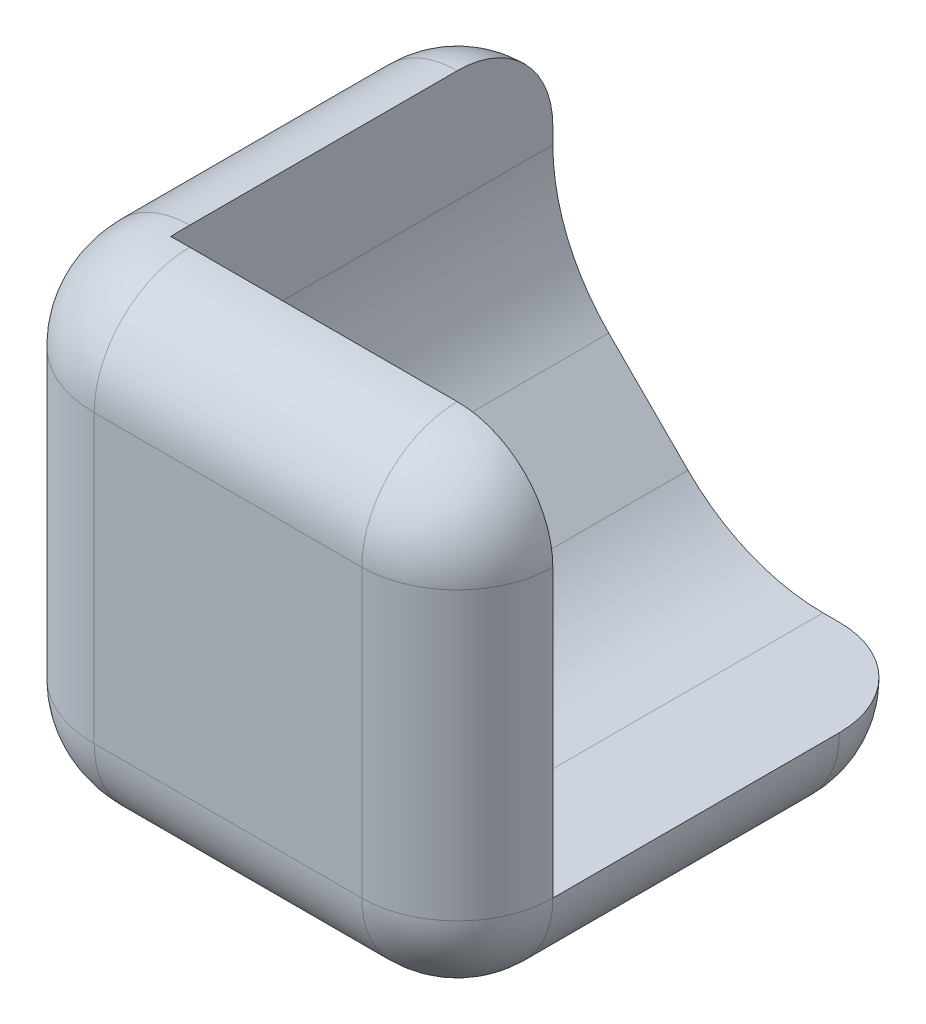
SolidWorks part; units mm, degrees
ref_plane "Front Plane" through (0, 0, 0) normal (0, 0, 1) x (1, 0, 0)
ref_plane "Top Plane" through (0, 0, 0) normal (0, 1, 0) x (1, 0, 0)
ref_plane "Right Plane" through (0, 0, 0) normal (1, 0, 0) x (0, 0, -1)
sketch "Sketch1" plane through (0, 0, 0) normal (0, 1, 0) x (1, 0, 0)
  line L1 (-10, 10) -> (10, 10)
  line L2 (-10, 10) -> (-10, -10)
  line L3 (-10, -10) -> (10, -10)
  line L4 (10, 10) -> (10, -10)
  line L5 (0, -10) -> (0, 10) construction
  line L6 (-10, 0) -> (10, 0) construction
  line L7 (20, 20) -> (0, 20)
  line L8 (20, 20) -> (20, 0)
  line L9 (20, 0) -> (0, 0)
  line L10 (0, 20) -> (0, 0)
  line L11 (10, 0) -> (10, 20) construction
  line L12 (20, 10) -> (0, 10) construction
  point P0 (0, 0)
  dimension "D1" = 20
  dimension "D2" = 20
extrude "Boss-Extrude1" add sketch "Sketch1" along normal blind 20 contours L10 L1 L2 L3 L4 L9 | L1 L10 L9 L4 region at (-1.6667, 0, 1.6667) region at (5, 0, -5)
sketch "Sketch2" plane through (0, 20, 0) normal (0, 1, 0) x (1, 0, 0)
  line L1 (20, 20) -> (0, 20)
  line L2 (20, 20) -> (20, 0)
  line L3 (20, 0) -> (0, 0)
  line L4 (0, 20) -> (0, 0)
  line L5 (10, 0) -> (10, 20) construction
  line L6 (20, 10) -> (0, 10) construction
  point P0 (10, 10)
extrude "Cut-Extrude1" cut sketch "Sketch2" against normal blind 10
sketch "Sketch3" plane through (0, 0, 0) normal (0, 0, -1) x (-1, 0, 0)
  line L0 (-10, 10) -> (-7.0711, 10)
  line L1 (-10, 10) -> (0, 10) construction
  line L2 (-3.5355, 11.4645) -> (-1.4645, 13.5355)
  line L3 (0, 10) -> (0, 20) construction
  line L4 (0, 17.0711) -> (0, 20)
  line L6 (0, 10) -> (-10, 10)
  line L7 (0, 10) -> (0, 20)
  arc A0 (-1.4645, 13.5355) -> (0, 17.0711) centre (-5, 17.0711) ccw
  arc A1 (-7.0711, 10) -> (-3.5355, 11.4645) centre (-7.0711, 15) ccw
  point P12 (0, 15)
  point P15 (-5, 10)
  line M3 (-10, 10) -> (0, 10)
  line M4 (0, 10) -> (0, 20)
  dimension "D2" = 5
  dimension "D1" = 5
extrude "Boss-Extrude2" add sketch "Sketch3" along normal blind 10 contours A1 A0 L2 M3 M4 region at (1.7496, 11.7496, 0)
sketch "Sketch4" plane through (0, 20, 0) normal (0, 1, 0) x (1, 0, 0)
  line L1 (22.5, 22.5) -> (-2.5, 22.5)
  line L2 (22.5, 22.5) -> (22.5, -2.5)
  line L3 (22.5, -2.5) -> (-2.5, -2.5)
  line L4 (-2.5, 22.5) -> (-2.5, -2.5)
  line L5 (10, -2.5) -> (10, 22.5) construction
  line L6 (22.5, 10) -> (-2.5, 10) construction
  line L7 (-10, 10) -> (10, 10)
  line L8 (-10, 10) -> (-10, -10)
  line L9 (-10, -10) -> (10, -10)
  line L10 (10, 10) -> (10, -10)
  point P0 (10, 10)
  line M4 (0, 10) -> (-10, 10)
  line M5 (-10, 10) -> (-10, -10)
  line M6 (-10, -10) -> (10, -10)
  line M7 (10, -10) -> (10, 0)
  dimension "D1" = 25
  dimension "D2" = 25
extrude "Cut-Extrude2" cut sketch "Sketch4" against normal blind 25 contours L4 L3 M4 M5 M6 M7 region at (-2.7828, 20, -3.75)
sketch "Sketch5" plane through (10, 0, 0) normal (1, 0, 0) x (0, 0, -1)
  line L0 (-2.5, 0) -> (-2.5, 20) construction
  line L1 (-2.5, 7.5) -> (10, 7.5)
  line L2 (-2.5, 7.5) -> (-2.5, 0)
  line L3 (-2.5, 0) -> (10, 0)
  line L4 (10, 7.5) -> (10, 0)
  line L5 (0, 10) -> (10, 10) construction
  dimension "D1" = 2.5
extrude "Cut-Extrude3" cut sketch "Sketch5" against normal blind 25
fillet "Fillet6" radius 3 1 edges at (-2.5, 13.75, 2.5)
fillet "Fillet7" radius 2.5 3 edges at (5.25, 20, 2.5) (-1.6213, 20, 1.6213) (-2.5, 20, -5.25)
fillet "Fillet8" radius 2.5 3 edges at (5.25, 7.5, 2.5) (-2.5, 7.5, -5.25) (-1.6213, 7.5, 1.6213)
fillet "Fillet9" radius 2.5 8 edges at (5, 7.5, -10) (-1.7678, 19.2678, -10) (-2.5, 13.75, -10) (10, 19.2678, 1.7678) (10, 13.75, 2.5) (10, 7.5, -5) (-1.7678, 8.2322, -10) (10, 8.2322, 1.7678)
fillet "Fillet10" radius 2.5 1 edges at (9.2678, 8.2322, -9.2678)
